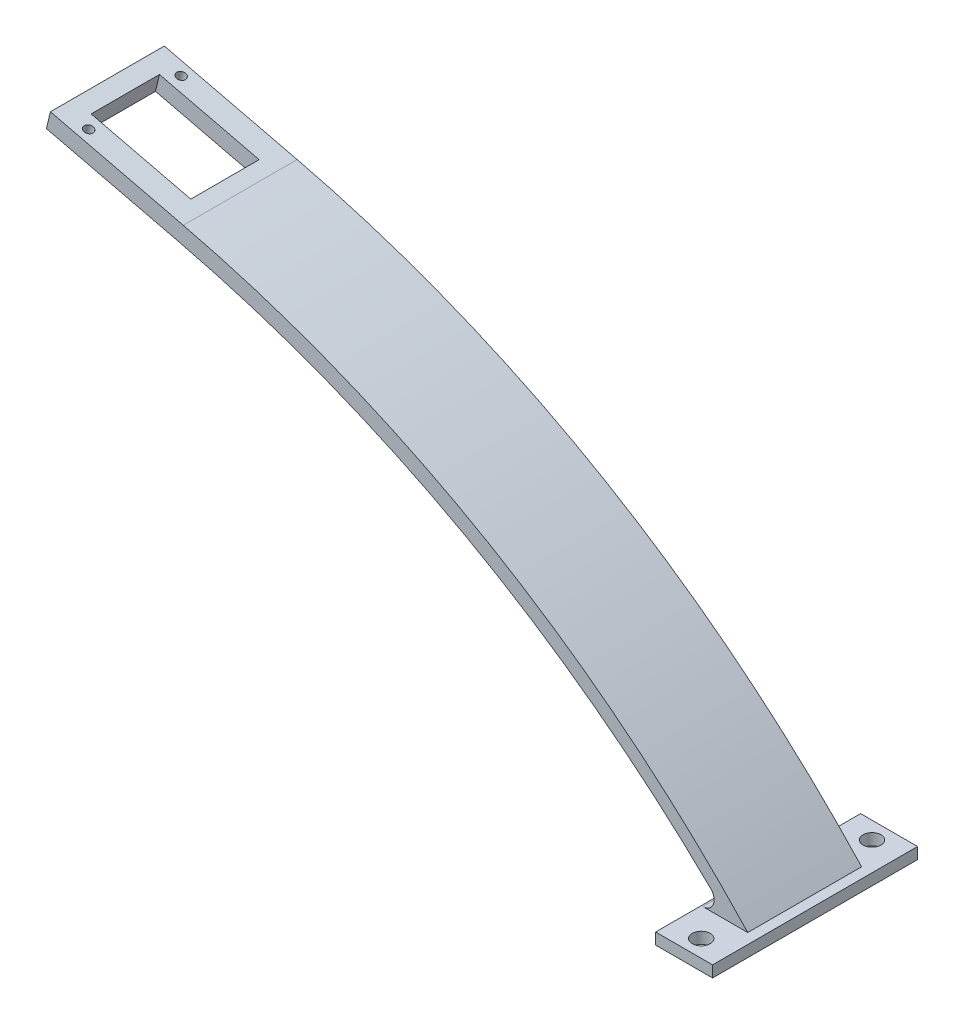
SolidWorks part; units mm, degrees
ref_plane "Front" through (0, 0, 0) normal (0, 0, 1) x (1, 0, 0)
ref_plane "Top" through (0, 0, 0) normal (0, 1, 0) x (1, 0, 0)
ref_plane "Right" through (0, 0, 0) normal (1, 0, 0) x (0, 0, -1)
sketch "Sketch1" plane through (0, 0, 0) normal (0, 0, 1) x (1, 0, 0)
  line L0 (-125.2866, 72.4953) -> (-154.9244, 79.6107)
  line L1 (-154.9244, 79.6107) -> (-154.035, 83.3154)
  line L2 (-154.035, 83.3154) -> (-124.3971, 76.2)
  line L3 (0, 0) -> (3.81, 0)
  line L4 (25.146, 0) -> (-25.146, 0) construction
  arc A0 (0, 0) -> (-125.2866, 72.4953) centre (-184.5817, -174.4867) ccw
  arc A1 (-124.3971, 76.2) -> (3.81, 0) centre (-183.1837, -168.6636) cw
  dimension "D3" = 254
  dimension "D4" = 13.5
  dimension "D1" = 3.81
  dimension "D2" = 3.81
  dimension "D5" = 30.48
  dimension "D6" = 30.48
  dimension "D7" = 76.2
extrude "Boss-Extrude1" add sketch "Sketch1" along normal blind 25.4
sketch "Sketch2" plane through (10.5178, 43.8098, 0) normal (0.2334, 0.9724, 0) x (0.9724, -0.2334, 0)
  line L0 (-169.2286, -25.4) -> (-169.2286, 0) construction
  line L1 (-165.1138, -5.08) -> (-142.2538, -5.08)
  line L2 (-165.1138, -5.08) -> (-165.1138, -20.32)
  line L3 (-165.1138, -20.32) -> (-142.2538, -20.32)
  line L4 (-142.2538, -5.08) -> (-142.2538, -20.32)
  line L5 (-169.2286, 0) -> (-169.2286, -25.4) construction
  line L6 (-45.9656, 0) -> (45.9656, 0) construction
  line L7 (-169.2286, -12.7) -> (-142.2538, -12.7) construction
  line L8 (-138.7486, -25.4) -> (-169.2286, -25.4) construction
  circle A0 centre (-162.8786, -2.4168) radius 0.9995
  circle A1 centre (-162.8786, -23.034) radius 0.9995
  point P12 (-169.2286, -12.7)
  point P13 (-165.1138, -12.7)
  dimension "D4" = 1.999
  dimension "D6" = 20.6172
  dimension "D7" = 6.35
  dimension "D1" = 22.86
  dimension "D2" = 15.24
  dimension "D3" = 4.1148
  dimension "D5" = 2.366
extrude "Cut-Extrude1" cut sketch "Sketch2" against normal up to next
sketch "Sketch3" plane through (0, 0, 0) normal (0, 1, 0) x (1, 0, 0)
  line L0 (-45.9656, 0) -> (45.9656, 0) construction
  line L1 (3.81, -35.56) -> (-8.89, -35.56)
  line L2 (3.81, -35.56) -> (3.81, 10.16)
  line L3 (3.81, 10.16) -> (-8.89, 10.16)
  line L4 (-8.89, -35.56) -> (-8.89, 10.16)
  line L5 (-124.3971, -25.4) -> (3.81, -25.4) construction
  line L6 (3.81, -25.4) -> (3.81, 0) construction
  circle A0 centre (-2.54, 6.35) radius 2
  circle A1 centre (-2.54, -31.75) radius 2
  dimension "D1" = 4
  dimension "D2" = 4
  dimension "D5" = 6.35
  dimension "D3" = 38.1
  dimension "D4" = 6.35
  dimension "D6" = 10.16
  dimension "D7" = 10.16
  dimension "D8" = 12.7
extrude "Boss-Extrude2" add sketch "Sketch3" along normal blind 2.54
fillet "Fillet1" radius 2.54 1 edges at (-2.4346, 2.54, 12.7)
